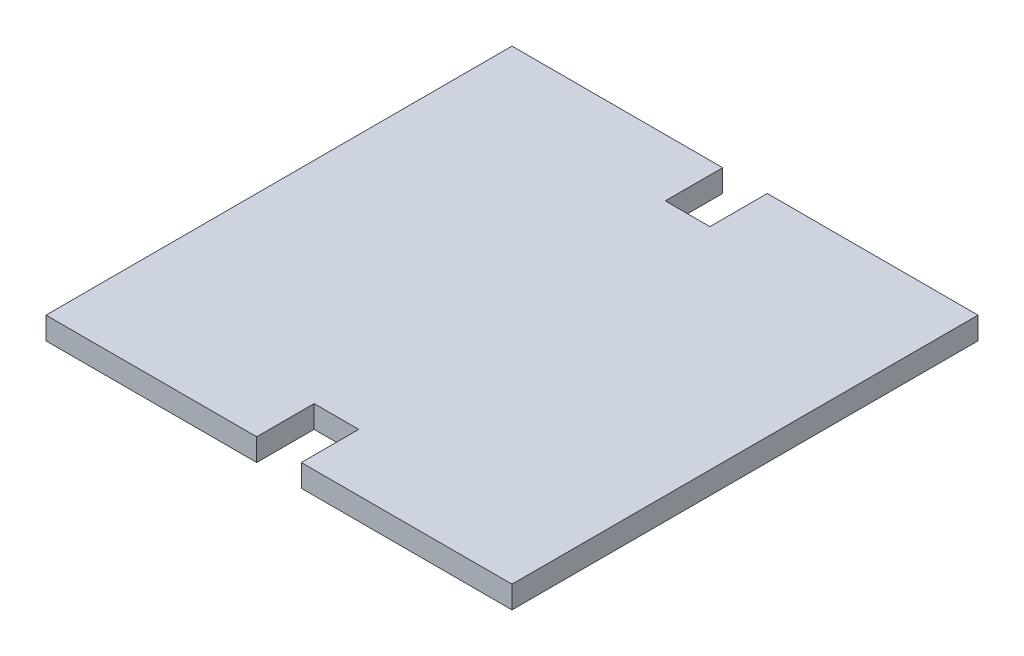
SolidWorks part; units mm, degrees
material "Acrylic (Medium-high impact)"
ref_plane "Front Plane" through (0, 0, 0) normal (0, 0, 1) x (1, 0, 0)
ref_plane "Top Plane" through (0, 0, 0) normal (0, 1, 0) x (1, 0, 0)
ref_plane "Right Plane" through (0, 0, 0) normal (1, 0, 0) x (0, 0, -1)
sketch "Sketch1" plane through (0, 0, 0) normal (0, 1, 0) x (1, 0, 0)
  line L1 (-66.35, -66.35) -> (66.35, -66.35)
  line L2 (-66.35, -66.35) -> (-66.35, 66.35)
  line L3 (-66.35, 66.35) -> (66.35, 66.35)
  line L4 (66.35, -66.35) -> (66.35, 66.35)
  line L5 (-66.35, -66.35) -> (66.35, 66.35) construction
  line L6 (-66.35, 66.35) -> (66.35, -66.35) construction
  point P0 (0, 0)
  dimension "D1" = 132.7
  dimension "D2" = 132.7
extrude "Boss-Extrude2" add sketch "Sketch1" along normal blind 6.35
ref_point "Point2"
ref_axis "Axis2" through (0, 6.35, 0) along (0, 1, 0)
sketch "Sketch4" plane through (0, 6.35, 0) normal (0, 1, 0) x (1, 0, 0)
  line L1 (-50, -50) -> (50, -50)
  line L2 (-50, -50) -> (-50, 50)
  line L3 (-50, 50) -> (50, 50)
  line L4 (50, -50) -> (50, 50)
  line L5 (-50, -50) -> (50, 50) construction
  line L6 (-50, 50) -> (50, -50) construction
  point P1 (0, 0)
  dimension "D1" = 100
  dimension "D2" = 100
sketch "Sketch5" plane through (0, 6.35, 0) normal (0, 1, 0) x (1, 0, 0)
  line L0 (-6.35, 50) -> (-6.35, 66.35)
  line L1 (-6.35, 50) -> (6.35, 50)
  line L2 (-6.35, 66.35) -> (6.35, 66.35)
  line L3 (6.35, 50) -> (6.35, 66.35)
  line L4 (-6.35, 50) -> (6.35, 66.35) construction
  line L5 (-6.35, 66.35) -> (6.35, 50) construction
  line L6 (66.35, 66.35) -> (-66.35, 66.35) construction
  line L7 (-66.35, 66.35) -> (-66.35, -66.35) construction
  point P1 (0, 58.175)
  dimension "D1" = 8.175
  dimension "D2" = 16.35
  dimension "D3" = 12.7
  dimension "D4" = 66.35
extrude "Cut-Extrude1" cut sketch "Sketch5" against normal through all
pattern_circular "CirPattern1" count 2 every 180 about axis through (0, 6.35, 0) along (0, 1, 0) of "Cut-Extrude1"
